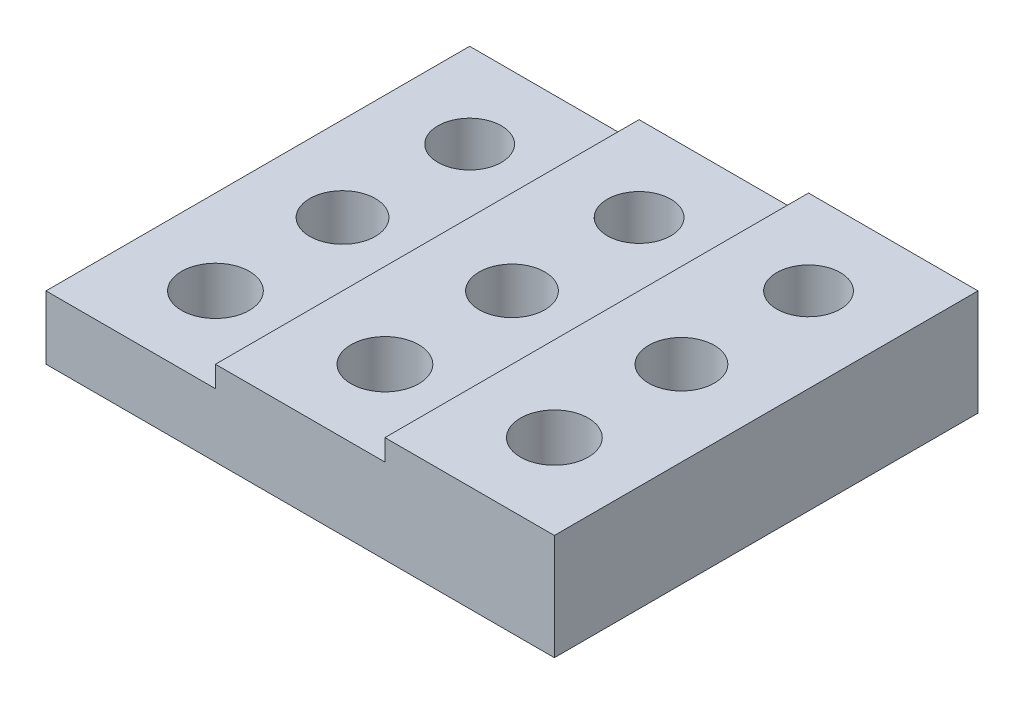
SolidWorks part; units mm, degrees
ref_plane "Front Plane" through (0, 0, 0) normal (0, 0, 1) x (1, 0, 0)
ref_plane "Top Plane" through (0, 0, 0) normal (0, 1, 0) x (1, 0, 0)
ref_plane "Right Plane" through (0, 0, 0) normal (1, 0, 0) x (0, 0, -1)
sketch "Sketch1" plane through (0, 0, 0) normal (0, 1, 0) x (1, 0, 0)
  line L0 (8, 0) -> (8, 20)
  line L1 (8, 0) -> (-8, 0)
  line L2 (0, 0) -> (0, 20)
  line L3 (8, 20) -> (-8, 20)
  line L4 (-8, 0) -> (-8, 20)
  line L5 (16, 0) -> (16, 20)
  line L6 (8, 20) -> (16, 20)
  line L7 (8, 0) -> (16, 0)
  circle A0 centre (-4, 4) radius 1.6
  circle A1 centre (-4, 16) radius 1.5
  circle A2 centre (4, 4) radius 1.6
  circle A3 centre (4, 16) radius 1.5
  circle A4 centre (12, 4) radius 1.6
  circle A5 centre (12, 16) radius 1.5
  circle A6 centre (-4, 10) radius 1.55
  circle A7 centre (4, 10) radius 1.55
  circle A8 centre (12, 10) radius 1.55
  dimension "D3" = 3.2
  dimension "D4" = 3
  dimension "D9" = 3.1
  dimension "D1" = 20
  dimension "D2" = 8
  dimension "D5" = 4
  dimension "D6" = 4
  dimension "D7" = 4
  dimension "D8" = 4
  dimension "D10" = 6
  dimension "D11" = 4
extrude "Boss-Extrude7" add sketch "Sketch1" along normal blind 5 contours L0 L7 L5 L6 A8 A5 A4 region at (8.2154, 0, -10)
extrude "Boss-Extrude8" add sketch "Sketch1<8>" along normal blind 4 contours L0 L3 L2 L1 A3 A2 A7 region at (4, 0, -0.2154)
sketch "Sketch1<8>" plane through (0, 0, 0) normal (0, 1, 0) x (1, 0, 0) same geometry as "Sketch1"
extrude "Boss-Extrude9" add sketch "Sketch1<9>" along normal blind 3 contours L4 L1 L2 L3 A6 A1 A0 region at (-4, 0, -0.2154)
sketch "Sketch1<9>" plane through (0, 0, 0) normal (0, 1, 0) x (1, 0, 0) same geometry as "Sketch1"
